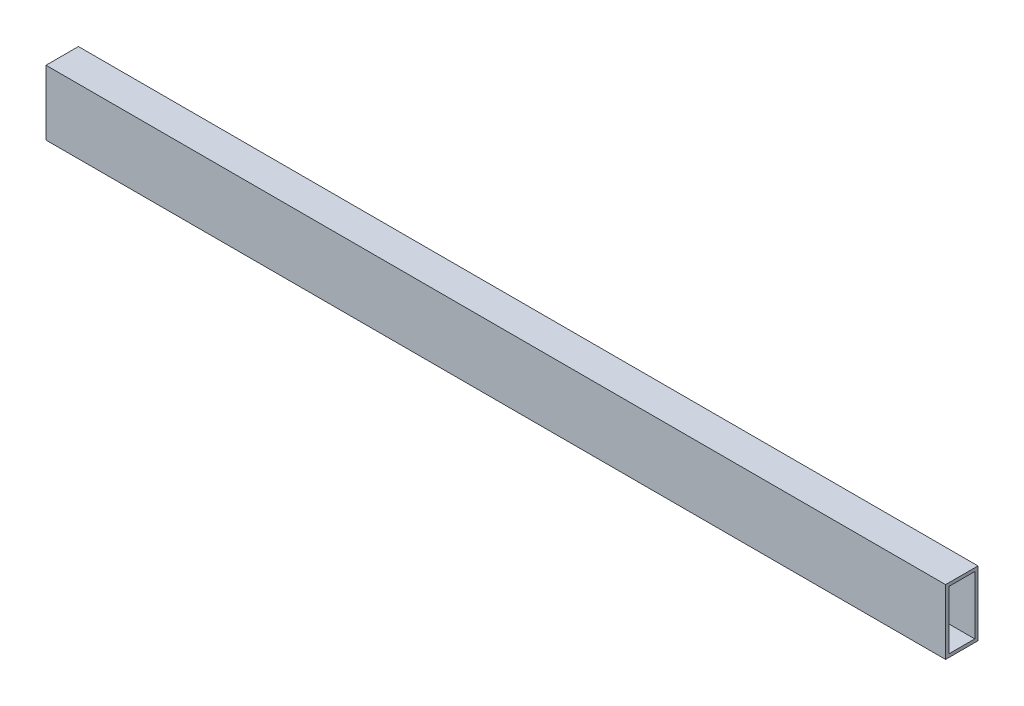
SolidWorks part; units mm, degrees
ref_plane "Front" through (0, 0, 0) normal (0, 0, 1) x (1, 0, 0)
ref_plane "Top" through (0, 0, 0) normal (0, 1, 0) x (1, 0, 0)
ref_plane "Right" through (0, 0, 0) normal (1, 0, 0) x (0, 0, -1)
sketch "Sketch1" plane through (0, 0, 0) normal (1, 0, 0) x (0, 0, -1)
  line L1 (-12.7, -25.4) -> (12.7, -25.4)
  line L2 (-12.7, -25.4) -> (-12.7, 25.4)
  line L3 (-12.7, 25.4) -> (12.7, 25.4)
  line L4 (12.7, -25.4) -> (12.7, 25.4)
  line L5 (-12.7, -25.4) -> (12.7, 25.4) construction
  line L6 (-12.7, 25.4) -> (12.7, -25.4) construction
  point P0 (0, 0)
  dimension "D1" = 50.8
  dimension "D2" = 25.4
extrude "Extrude-Thin1" add sketch "Sketch1" along normal blind 704.85 thin thin type one direction reverse wall 2.54
